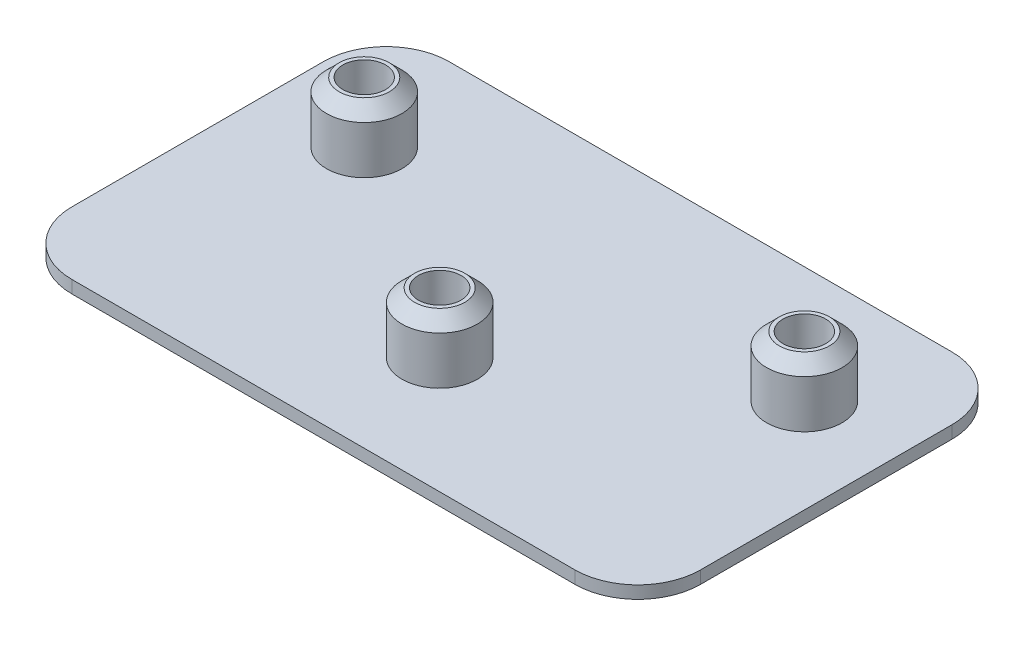
SolidWorks part; units mm, degrees
ref_plane "前视基准面" through (0, 0, 0) normal (0, 0, 1) x (1, 0, 0)
ref_plane "上视基准面" through (0, 0, 0) normal (0, 1, 0) x (1, 0, 0)
ref_plane "右视基准面" through (0, 0, 0) normal (1, 0, 0) x (0, 0, -1)
sketch "草图1" plane through (0, 0, 0) normal (0, 1, 0) x (1, 0, 0)
  line L0 (-17.5, 5.75) -> (17.5, 5.75)
  line L1 (-25, 15) -> (25, 15)
  line L2 (-25, 15) -> (-25, -15)
  line L3 (-25, -15) -> (25, -15)
  line L4 (25, 15) -> (25, -15)
  line L5 (0, -15) -> (0, 15) construction
  line L6 (-25, 0) -> (25, 0) construction
  line L7 (0, -5.75) -> (0, 5.75) construction
  circle A0 centre (-17.5, 5.75) radius 3
  circle A1 centre (17.5, 5.75) radius 3
  circle A2 centre (0, -5.75) radius 3
  point P0 (0, 0)
  point P10 (0, 0)
  dimension "D3" = 6
  dimension "D1" = 11.5
  dimension "D2" = 35
  dimension "D4" = 50
  dimension "D5" = 30
extrude "凸台-拉伸1" add sketch "草图1" along normal blind 1 contours L1 L4 L3 L2
extrude "凸台-拉伸2" add sketch "草图1<3>" along normal blind 5.8 contours A0 | A1 | A2
sketch "草图1<3>" plane through (0, 0, 0) normal (0, 1, 0) x (1, 0, 0) same geometry as "草图1"
hole_wizard "M3 平头机械螺钉的锥形沉头孔1" positions "草图2" profile "草图3" countersink size "M3" standard "ANSI Metric"
sketch "草图2" plane through (0, 0, 0) normal (0, -1, 0) x (-1, 0, 0)
  circle A0 centre (0, -5.75) radius 3 construction
  circle A1 centre (17.5, 5.75) radius 3 construction
  circle A2 centre (-17.5, 5.75) radius 3 construction
  circle A3 centre (0, -5.75) radius 3 construction
  circle A4 centre (17.5, 5.75) radius 3 construction
  circle A5 centre (-17.5, 5.75) radius 3 construction
  point P0 (-17.5, 5.75)
  point P3 (0, -5.75)
  point P5 (17.5, 5.75)
sketch "草图3" plane through (17.5, 0, -5.75) normal (1, 0, 0) x (0, 0, -1)
  line L0 (0, 0) -> (0, 8.5215)
  line L1 (0, 8.5215) -> (1.7, 7.5)
  line L2 (1.7, 7.5) -> (1.7, 1.5)
  line L3 (1.7, 1.5) -> (3.2, 0)
  line L5 (3.2, 0) -> (0, 0)
  line L6 (-1.7, 1.5) -> (-3.2, 0) construction
  line L10 (0, 8.5215) -> (-1.7, 7.5) construction
  line L11 (0, -6.35) -> (0, 107.95) construction
  dimension "孔直径" = 3.4
  dimension "孔深度" = 7.5
  dimension "近端锥形沉头孔直径" = 6.4
  dimension "近端锥形沉头孔角度" = 90
  dimension "导头角度" = 118
chamfer "倒角1" distance 1 angle 45 3 edges at (-17.5, 5.8, -2.75) (0, 5.8, 8.75) (17.5, 5.8, -2.75)
fillet "圆角1" radius 5 4 edges at (-25, 0.5, 15) (-25, 0.5, -15) (25, 0.5, -15) (25, 0.5, 15)
